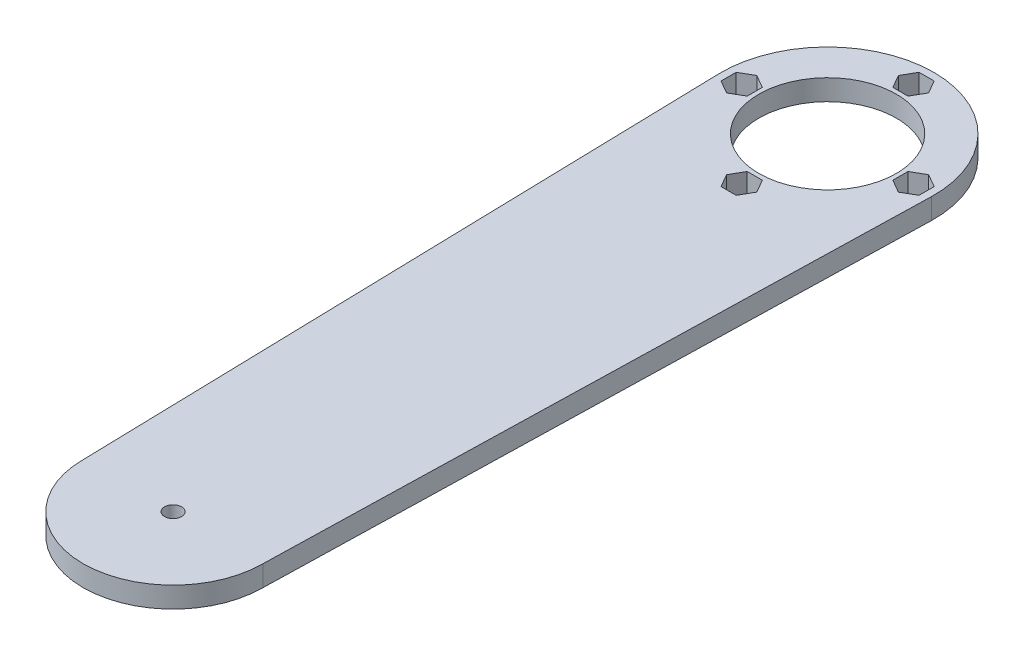
SolidWorks part; units mm, degrees
ref_plane "Front Plane" through (0, 0, 0) normal (0, 0, 1) x (1, 0, 0)
ref_plane "Top Plane" through (0, 0, 0) normal (0, 1, 0) x (1, 0, 0)
ref_plane "Right Plane" through (0, 0, 0) normal (1, 0, 0) x (0, 0, -1)
sketch "Sketch1" plane through (0, 0, 0) normal (0, 1, 0) x (1, 0, 0)
  line L0 (27.5, 0) -> (32.4898, 199.1861)
  line L1 (-27.5, 0) -> (-32.4898, 199.1861)
  arc A0 (-27.5, 0) -> (27.5, 0) centre (0, 0) ccw
  arc A3 (32.4898, 199.1861) -> (-32.4898, 199.1861) centre (0, 200) ccw
  dimension "D1" = 55
  dimension "D3" = 200
  dimension "D2" = 65
extrude "Boss-Extrude1" add sketch "Sketch1" along normal blind 6.35 contours A0 | A0 region at (0, 0, -106.0304)
sketch "Sketch2" plane through (0, 6.35, 0) normal (0, 1, 0) x (1, 0, 0)
  circle A0 centre (0, 0) radius 2.6
  dimension "D1" = 5.2
extrude "Cut-Extrude1" cut sketch "Sketch2" against normal through all
sketch "Esquisse4" plane through (0, 6.35, 0) normal (0, 1, 0) x (1, 0, 0)
  circle A0 centre (0, 200) radius 32.5
  arc A1 (32.4898, 199.1861) -> (-32.4898, 199.1861) centre (0, 200) ccw construction
sketch "Esquisse3" plane through (0, 6.35, 0) normal (0, 1, 0) x (1, 0, 0)
  circle A1 centre (0, 200) radius 21
  dimension "D1" = 42
extrude "Enlèv. mat.-Extru.2" cut sketch "Esquisse3" against normal through all
sketch "Esquisse5" plane through (0, 6.35, 0) normal (0, 1, 0) x (1, 0, 0)
  circle A0 centre (0, 200) radius 26.25
  dimension "D1" = 52.5
sketch "Esquisse7" plane through (0, 6.35, 0) normal (0, 1, 0) x (1, 0, 0)
  circle A0 centre (0, 226.25) radius 4
  circle A1 centre (0, 200) radius 26.25 construction
  circle A2 centre (26.25, 200) radius 4
  circle A3 centre (0, 173.75) radius 4
  circle A4 centre (-26.25, 200) radius 4
  dimension "D1" = 8
extrude "Enlèv. mat.-Extru.3" cut sketch "Esquisse7" against normal through all
sketch "Esquisse10" plane through (0, 0, 0) normal (1, 0, 0) x (0, 0, -1)
  line L0 (200, 30.779) -> (200, -18.079) construction
  point P2 (200, 84.0849)
  point P4 (200, 6.35)
sketch "Esquisse8" plane through (0, 6.35, 0) normal (0, 1, 0) x (1, 0, 0)
  line L0 (-2.3094, 177.75) -> (2.3094, 177.75)
  line L1 (2.3094, 177.75) -> (4.6188, 173.75)
  line L2 (4.6188, 173.75) -> (2.3094, 169.75)
  line L3 (2.3094, 169.75) -> (-2.3094, 169.75)
  line L4 (-2.3094, 169.75) -> (-4.6188, 173.75)
  line L5 (-4.6188, 173.75) -> (-2.3094, 177.75)
  line L6 (0, -3.4925) -> (0, 3.4925) construction
  circle A1 centre (0, 173.75) radius 4 construction
extrude "Enlèv. mat.-Extru.5" cut sketch "Esquisse8" against normal through all
pattern_circular "Répétition circulaire1" count 4 over 360 about axis through (0, 30.779, -200) along (0, -1, 0) of "Enlèv. mat.-Extru.5"
